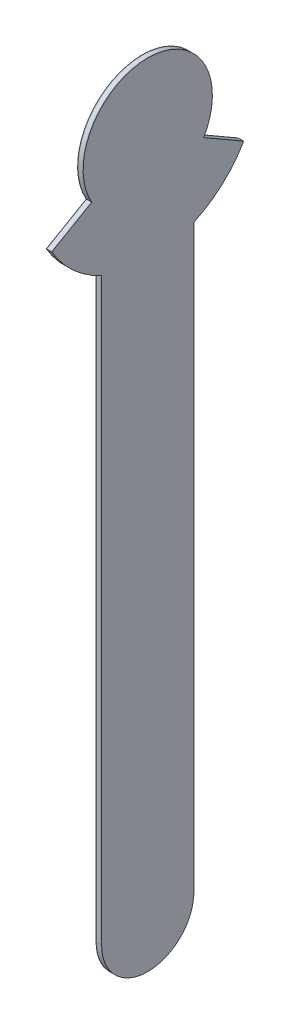
SolidWorks part; units mm, degrees
ref_plane "Front Plane" through (0, 0, 0) normal (0, 0, 1) x (1, 0, 0)
ref_plane "Top Plane" through (0, 0, 0) normal (0, 1, 0) x (1, 0, 0)
ref_plane "Right Plane" through (0, 0, 0) normal (1, 0, 0) x (0, 0, -1)
sketch "Sketch1" plane through (0, 0, 0) normal (1, 0, 0) x (0, 0, -1)
  line L0 (0, -35) -> (0, -393.6) construction
  line L2 (-25, -368.6) -> (-25, -54.5436)
  line L3 (25, -368.6) -> (25, -54.5436)
  line L4 (-30.3109, -17.5) -> (-51.9615, -30)
  line L5 (30.3109, -17.5) -> (51.9615, -30)
  line L6 (-14.9027, 0) -> (13.6443, 0) construction
  arc A0 (-51.9615, -30) -> (51.9615, -30) centre (0, 0) ccw
  circle A1 centre (0, 0) radius 35
  arc A2 (-25, -368.6) -> (25, -368.6) centre (0, -368.6) ccw
  point P8 (0, -393.6)
  dimension "D1" = 120
  dimension "D2" = 70
  dimension "D7" = 50
  dimension "D3" = 393.6
  dimension "D5" = 30
  dimension "D6" = 30
extrude "Boss-Extrude1" add sketch "Sketch1" against normal blind 0.25 contours A0 L2 L3 | A1 L4 A0 L5 | A1 region at (0, -223.2685, 0) region at (0, -40.189, 0) region at (0, 0, 0)
sketch "Sketch2" plane through (-0.25, 0, 0) normal (-1, 0, 0) x (0, 0, 1)
  line L4 (25, -368.6) -> (25, -54.5436)
  line L5 (51.9615, -30) -> (30.3109, -17.5)
  line L6 (-30.3109, -17.5) -> (-51.9615, -30)
  line L7 (-25, -54.5436) -> (-25, -368.6)
  line L8 (25, -368.6) -> (25, -54.5436)
  line L9 (51.9615, -30) -> (30.3109, -17.5)
  line L10 (-30.3109, -17.5) -> (-51.9615, -30)
  line L11 (-25, -54.5436) -> (-25, -368.6)
  arc A4 (25, -54.5436) -> (51.9615, -30) centre (0, 0) ccw
  arc A5 (30.3109, -17.5) -> (-30.3109, -17.5) centre (0, 0) ccw
  arc A6 (-51.9615, -30) -> (-25, -54.5436) centre (0, 0) ccw
  arc A7 (-25, -368.6) -> (25, -368.6) centre (0, -368.6) ccw
  arc A8 (25, -54.5436) -> (51.9615, -30) centre (0, 0) ccw
  arc A9 (30.3109, -17.5) -> (-30.3109, -17.5) centre (0, 0) ccw
  arc A10 (-51.9615, -30) -> (-25, -54.5436) centre (0, 0) ccw
  arc A11 (-25, -368.6) -> (25, -368.6) centre (0, -368.6) ccw
  dimension "D1" = 0
extrude "Boss-Extrude2" add sketch "Sketch2" along normal blind 2.5 separate body
sketch "Sketch3" plane through (-2.75, 0, 0) normal (-1, 0, 0) x (0, 0, 1)
  line L4 (25, -368.6) -> (25, -54.5436)
  line L5 (51.9615, -30) -> (30.3109, -17.5)
  line L6 (-30.3109, -17.5) -> (-51.9615, -30)
  line L7 (-25, -54.5436) -> (-25, -368.6)
  line L8 (25, -368.6) -> (25, -54.5436)
  line L9 (51.9615, -30) -> (30.3109, -17.5)
  line L10 (-30.3109, -17.5) -> (-51.9615, -30)
  line L11 (-25, -54.5436) -> (-25, -368.6)
  arc A4 (-25, -368.6) -> (25, -368.6) centre (0, -368.6) ccw
  arc A5 (25, -54.5436) -> (51.9615, -30) centre (0, 0) ccw
  arc A6 (30.3109, -17.5) -> (-30.3109, -17.5) centre (0, 0) ccw
  arc A7 (-51.9615, -30) -> (-25, -54.5436) centre (0, 0) ccw
  arc A8 (-25, -368.6) -> (25, -368.6) centre (0, -368.6) ccw
  arc A9 (25, -54.5436) -> (51.9615, -30) centre (0, 0) ccw
  arc A10 (30.3109, -17.5) -> (-30.3109, -17.5) centre (0, 0) ccw
  arc A11 (-51.9615, -30) -> (-25, -54.5436) centre (0, 0) ccw
  dimension "D1" = 0
extrude "Boss-Extrude3" add sketch "Sketch3" along normal blind 0.25 separate body
